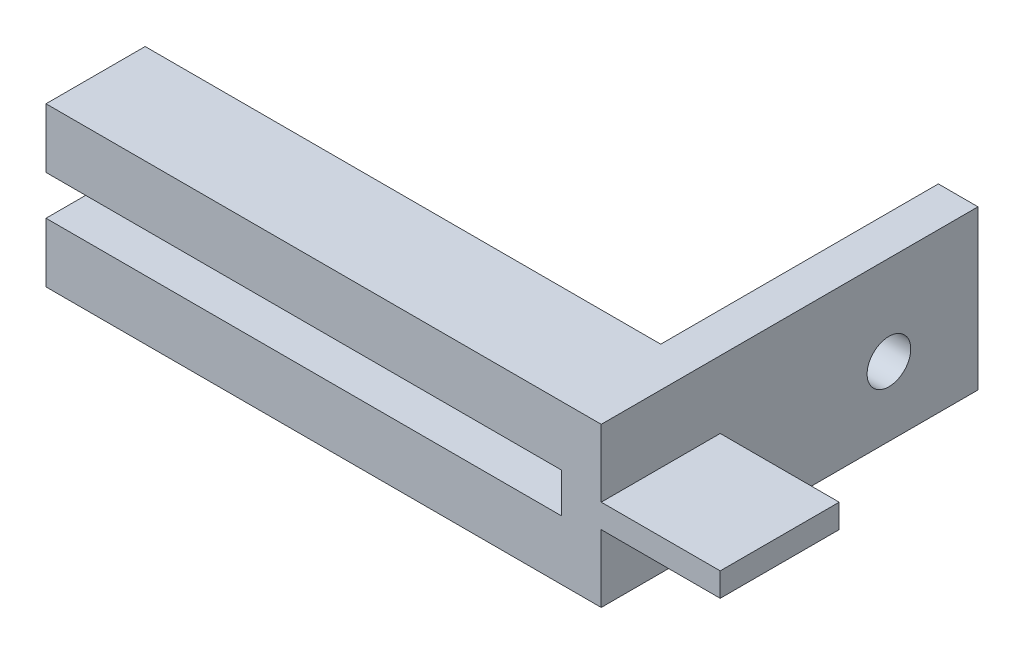
SolidWorks part; units mm, degrees
ref_plane "Front Plane" through (0, 0, 0) normal (0, 0, 1) x (1, 0, 0)
ref_plane "Top Plane" through (0, 0, 0) normal (0, 1, 0) x (1, 0, 0)
ref_plane "Right Plane" through (0, 0, 0) normal (1, 0, 0) x (0, 0, -1)
sketch "Sketch1" plane through (0, 0, 0) normal (1, 0, 0) x (0, 0, -1)
  line L1 (-35.9146, 20.1296) -> (59.0854, 20.1296)
  line L2 (-35.9146, 20.1296) -> (-35.9146, -19.8704)
  line L3 (-35.9146, -19.8704) -> (59.0854, -19.8704)
  line L4 (59.0854, 20.1296) -> (59.0854, -19.8704)
  dimension "D1" = 95
  dimension "D2" = 40
extrude "Boss-Extrude1" add sketch "Sketch1" along normal blind 10
sketch "Sketch4" plane through (0, 0, 0) normal (-1, 0, 0) x (0, 0, 1)
  line L0 (-59.0854, 20.1296) -> (35.9146, 20.1296) construction
  line L1 (10.9146, 20.1296) -> (35.9146, 20.1296)
  line L2 (10.9146, 20.1296) -> (10.9146, 5.1296)
  line L3 (10.9146, 5.1296) -> (35.9146, 5.1296)
  line L4 (35.9146, 20.1296) -> (35.9146, 5.1296)
  line L5 (35.9146, 20.1296) -> (35.9146, -19.8704) construction
  line L6 (35.9146, -19.8704) -> (-59.0854, -19.8704) construction
  line L7 (35.9146, -4.8704) -> (10.9146, -4.8704)
  line L8 (35.9146, -4.8704) -> (35.9146, -19.8704)
  line L9 (35.9146, -19.8704) -> (10.9146, -19.8704)
  line L10 (10.9146, -4.8704) -> (10.9146, -19.8704)
  dimension "D1" = 25
  dimension "D2" = 10
  dimension "D3" = 25
  dimension "D4" = 15
extrude "Boss-Extrude4" add sketch "Sketch4" along normal blind 130
sketch "Sketch5" plane through (0, 0, 0) normal (-1, 0, 0) x (0, 0, 1)
  line L0 (10.9146, -19.8704) -> (-59.0854, -19.8704) construction
  line L1 (-59.0854, -19.8704) -> (-59.0854, 20.1296) construction
  circle A0 centre (-36.6254, -2.4304) radius 5.5
  dimension "D1" = 11
  dimension "D2" = 17.44
  dimension "D3" = 22.46
extrude "Cut-Extrude1" cut sketch "Sketch5" against normal blind 27
sketch "Sketch6" plane through (10, 0, 0) normal (1, 0, 0) x (0, 0, -1)
  line L0 (-35.9146, 20.1296) -> (-35.9146, -19.8704) construction
  line L1 (-5.9146, -2.8704) -> (-35.9146, -2.8704)
  line L2 (-5.9146, -2.8704) -> (-5.9146, 3.1296)
  line L3 (-5.9146, 3.1296) -> (-35.9146, 3.1296)
  line L4 (-35.9146, -2.8704) -> (-35.9146, 3.1296)
  line L5 (-5.9146, -2.8704) -> (-35.9146, 3.1296) construction
  line L6 (-5.9146, 3.1296) -> (-35.9146, -2.8704) construction
  line L8 (-35.9146, -19.8704) -> (59.0854, -19.8704) construction
  point P0 (-20.9146, 0.1296)
  dimension "D1" = 30
  dimension "D2" = 6
  dimension "D3" = 20
extrude "Boss-Extrude5" add sketch "Sketch6" along normal blind 30
